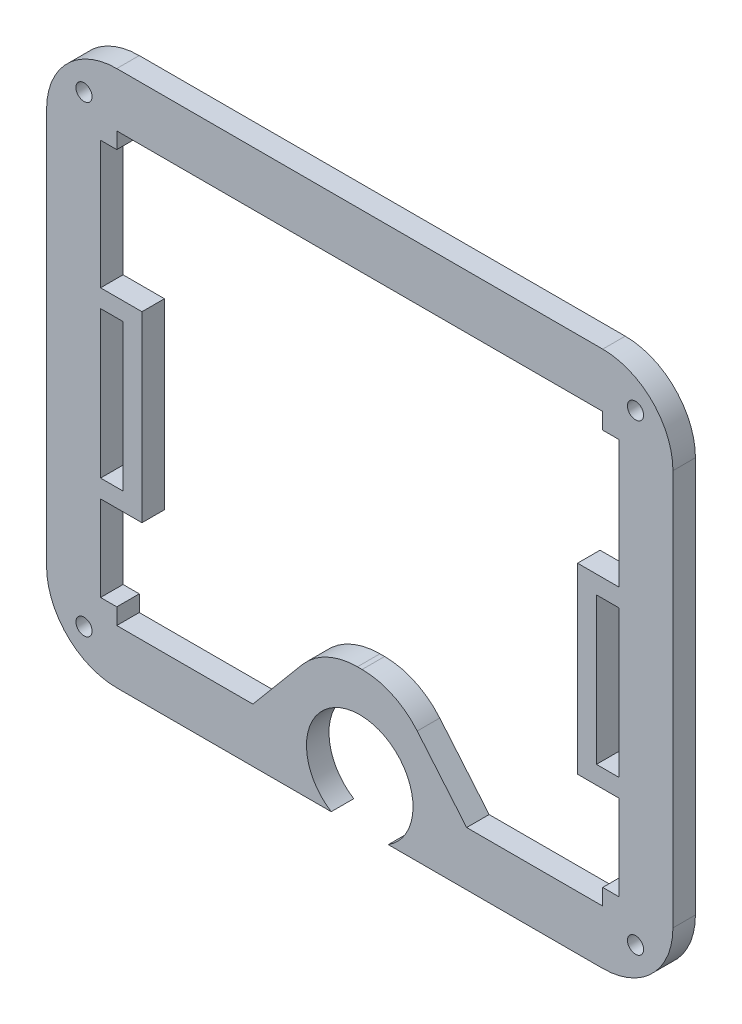
SolidWorks part; units mm, degrees
material "Delrin"
ref_plane "Front Plane" through (0, 0, 0) normal (0, 0, 1) x (1, 0, 0)
ref_plane "Top Plane" through (0, 0, 0) normal (0, 1, 0) x (1, 0, 0)
ref_plane "Right Plane" through (0, 0, 0) normal (1, 0, 0) x (0, 0, -1)
sketch "Sketch1" plane through (0, 0, 0) normal (0, 0, 1) x (1, 0, 0)
  line L0 (-17.145, -18.923) -> (-2.0127, -18.923)
  line L1 (-18.288, 13.97) -> (-18.288, -13.97)
  line L2 (-17.145, -15.113) -> (-7.5425, -15.113)
  line L3 (7.5425, -15.113) -> (17.145, -15.113)
  line L4 (18.288, 13.97) -> (18.288, -13.97)
  line L5 (-1000, 0) -> (49000, 0) construction
  line L6 (26.8751, -22.5509) -> (-27.4868, 23.0642) construction
  line L7 (2.0127, -18.923) -> (17.145, -18.923)
  line L8 (17.145, 15.113) -> (-17.145, 15.113)
  line L9 (-7.5425, -15.113) -> (-4.0566, -10.9586)
  line L10 (-22.098, 13.97) -> (-22.098, -13.97)
  line L11 (7.5425, -15.113) -> (4.0566, -10.9586)
  line L12 (-0.1651, -9.144) -> (0.1651, -9.144)
  line L13 (22.098, 13.97) -> (22.098, -13.97)
  line L14 (17.145, 18.923) -> (-17.145, 18.923)
  line L15 (-17.145, -13.97) -> (-17.145, -15.113)
  line L16 (-18.288, 13.97) -> (-17.145, 13.97)
  line L17 (-18.288, -13.97) -> (-17.145, -13.97)
  line L18 (0, 12.5532) -> (0, -24.2768) construction
  line L19 (17.145, 15.113) -> (17.145, 13.97)
  line L20 (-17.145, 13.97) -> (-17.145, 15.113)
  line L21 (17.145, 13.97) -> (18.288, 13.97)
  line L22 (17.145, -15.113) -> (17.145, -13.97)
  line L23 (17.145, -13.97) -> (18.288, -13.97)
  arc A0 (2.0127, -18.923) -> (-2.0127, -18.923) centre (0, -15.748) ccw
  arc A1 (-17.145, -15.113) -> (-18.288, -13.97) centre (-17.145, -13.97) cw construction
  arc A2 (-0.1651, -9.144) -> (-4.0566, -10.9586) centre (-0.1651, -14.224) ccw
  arc A3 (18.288, -13.97) -> (17.145, -15.113) centre (17.145, -13.97) cw construction
  arc A4 (17.145, 15.113) -> (18.288, 13.97) centre (17.145, 13.97) cw construction
  arc A5 (-17.145, -18.923) -> (-22.098, -13.97) centre (-17.145, -13.97) cw
  arc A6 (22.098, -13.97) -> (17.145, -18.923) centre (17.145, -13.97) cw
  arc A7 (17.145, 18.923) -> (22.098, 13.97) centre (17.145, 13.97) cw
  arc A8 (-17.145, 18.923) -> (-22.098, 13.97) centre (-17.145, 13.97) ccw
  circle A9 centre (-19.4575, 16.3268) radius 0.5715
  circle A10 centre (19.4575, 16.3268) radius 0.5715
  arc A11 (-17.145, 15.113) -> (-18.288, 13.97) centre (-17.145, 13.97) ccw construction
  arc A12 (0.1651, -9.144) -> (4.0566, -10.9586) centre (0.1651, -14.224) cw
  circle A13 centre (19.4575, -16.3268) radius 0.5715
  circle A14 centre (-19.4575, -16.3268) radius 0.5715
  arc A18 (7.5425, -15.113) -> (-7.5425, -15.113) centre (0, -15.748) ccw construction
  point P0 (0, 0)
  dimension "D4" = 3.175
  dimension "D6" = 37.846
  dimension "D7" = 44.196
  dimension "D8" = 3.81
  dimension "D9" = 6.604
  dimension "D5" = 1.143
  dimension "D2" = 4.953
  dimension "D3" = 7.5184
  dimension "D10" = 5.08
  dimension "D11" = 5.08
  dimension "D12" = 25.4
  dimension "D13" = 40
extrude "Boss-Extrude1" add sketch "Sketch1" along normal blind 1.5875
sketch "Sketch2" plane through (-18.288, 0, 0) normal (1, 0, 0) x (0, 0, -1)
  line L0 (0, 3.6831) -> (-1.5875, 3.6831)
  line L1 (0, -6.6742) -> (-1.5875, -6.6742) construction
  line L3 (-1.5875, -15.113) -> (0, -15.113)
  line L4 (0, -13.97) -> (0, 13.97)
  line L5 (0, 13.97) -> (-1.5875, 13.97)
  line L6 (-1.5875, 13.97) -> (-1.5875, -13.97)
  line L7 (-1.5875, -13.97) -> (0, -13.97)
  line L8 (0, -13.97) -> (0, 4.9531)
  line L9 (-1.5875, -15.113) -> (-1.5875, -7.9442)
  line L10 (-1.5875, 4.9531) -> (-1.5875, -13.97)
  line L11 (-1.5875, -13.97) -> (0, -13.97)
  line L12 (0, -15.113) -> (0, -7.9442)
  line L13 (0, 4.9531) -> (-1.5875, 4.9531)
  line L15 (-1.5875, 4.9531) -> (-1.5875, 3.6831)
  line L16 (0, 3.6831) -> (0, 4.9531)
  line L17 (0, -7.9147) -> (0, 1.1431)
  line L18 (-1.5875, -7.9147) -> (-1.5875, -6.6447)
  line L19 (0, -6.6742) -> (-1.5875, -6.6742)
  line L21 (0, -7.9442) -> (-1.5875, -7.9442)
  line L22 (0, -7.9442) -> (0, -13.97)
  line L23 (-1.5875, -7.9442) -> (-1.5875, -13.97)
  line L24 (37.1281, 3.5051) -> (-36.4799, 3.858) construction
  line L25 (31.9354, 0.99) -> (-32.9001, 1.3008) construction
  line L26 (-1.5875, -15.113) -> (0, -15.113) construction
  line L29 (36.5776, -9.5806) -> (-36.8, -3.75) construction
  line M5 (0, -13.97) -> (0, 13.97)
  line M7 (-1.5875, 13.97) -> (-1.5875, -13.97)
  dimension "D1" = 0
  dimension "D2" = 1.27
  dimension "D4" = 1.27
extrude "Boss-Extrude2" add sketch "Sketch2" along normal blind 2.921 contours L13 L10 L0 M5 | L19 L17 L8 L0 L10 M7 | L21 L8 L19 L18 M5 M7 region at (-18.288, -1.4955, 0.7937) region at (-18.288, 4.3181, 0.7937) region at (-18.288, -7.3092, 0.7937)
extrude "Cut-Extrude1" cut sketch "Sketch2<3>" along normal blind 1.5875 contours L19 L8 L10 region at (-18.288, -1.4955, 0.7937)
sketch "Sketch2<3>" plane through (-18.288, 0, 0) normal (1, 0, 0) x (0, 0, -1) same geometry as "Sketch2"
mirror "Mirror1" about plane through (0, 0, 0) normal (1, 0, 0) of "Cut-Extrude1", "Boss-Extrude2"
